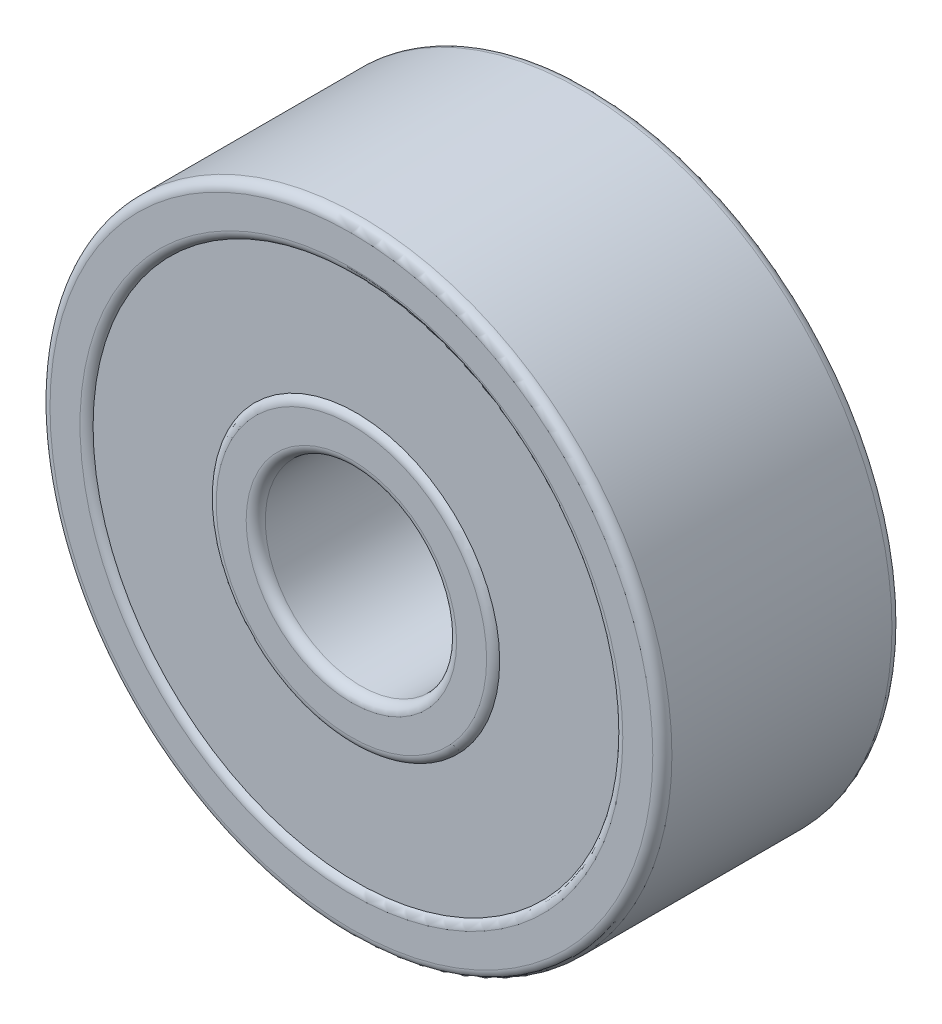
SolidWorks part; units mm, degrees
material "AISI 4340 Acier normalisé"
ref_plane "Plan de face" through (0, 0, 0) normal (0, 0, 1) x (1, 0, 0)
ref_plane "Plan de dessus" through (0, 0, 0) normal (0, 1, 0) x (1, 0, 0)
ref_plane "Plan de droite" through (0, 0, 0) normal (1, 0, 0) x (0, 0, -1)
sketch "Esquisse1" plane through (0, 0, 0) normal (0, 0, 1) x (1, 0, 0)
  circle A0 centre (0, 0) radius 6.5
  circle A1 centre (0, 0) radius 2
  circle A2 centre (0, 0) radius 3
  circle A3 centre (0, 0) radius 5.5
  dimension "D1" = 4
  dimension "D2" = 13
  dimension "D3" = 6
  dimension "D4" = 11
extrude "Boss.-Extru.1" add sketch "Esquisse1" along normal blind 5 contours A0 A3 | A3 A2 | A2 A1 region at (-6.3162, 0, 0) region at (-2.9151, 0, 0) region at (-5.3444, 0, 0)
extrude "Enlèv. mat.-Extru.1" cut sketch "Esquisse1<3>" along normal blind 0.1 contours A3 A2 region at (-5.3444, 0, 0)
sketch "Esquisse1<3>" plane through (0, 0, 0) normal (0, 0, 1) x (1, 0, 0) same geometry as "Esquisse1"
sketch "Esquisse2" plane through (0, 0, 5) normal (0, 0, 1) x (1, 0, 0)
  circle A0 centre (0, 0) radius 3
  circle A1 centre (0, 0) radius 5.5
  dimension "D1" = 6
  dimension "D2" = 11
extrude "Enlèv. mat.-Extru.2" cut sketch "Esquisse2" against normal blind 0.1
fillet "Congé1" radius 0.2 8 edges at (2, 0, 0) (2, 0, 5) (6.5, 0, 0) (6.5, 0, 5) (3, 0, 0) (5.5, 0, 0) (3, 0, 5) (5.5, 0, 5)
